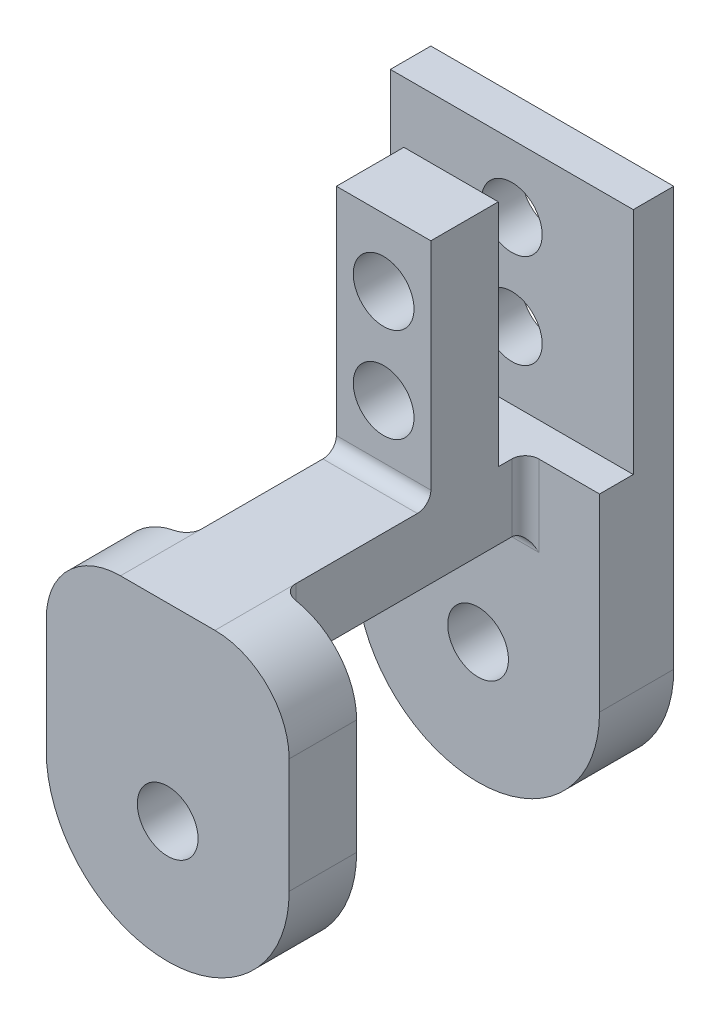
SolidWorks part; units mm, degrees
ref_plane "Plan de face" through (0, 0, 0) normal (0, 0, 1) x (1, 0, 0)
ref_plane "Plan de dessus" through (0, 0, 0) normal (0, 1, 0) x (1, 0, 0)
ref_plane "Plan de droite" through (0, 0, 0) normal (1, 0, 0) x (0, 0, -1)
sketch "Esquisse1" plane through (0, 0, 0) normal (0, 0, 1) x (1, 0, 0)
  line L0 (0, 17) -> (20, 17)
  line L1 (0, 0) -> (20, 0)
  line L2 (0, 0) -> (0, 25.6902)
  line L3 (0, 25.6902) -> (20, 25.6902)
  line L4 (20, 0) -> (20, 25.6902)
  circle A0 centre (10, 5) radius 2.1
  circle A1 centre (10, 12) radius 2.1
  point P15 (4.1099, 9.5645)
  dimension "D2" = 4.2
  dimension "D3" = 4.2
  dimension "D1" = 20
  dimension "D5" = 10
  dimension "D6" = 5
  dimension "D7" = 7
  dimension "D9" = 17
  dimension "D11" = 10
extrude "Boss.-Extru.1" add sketch "Esquisse1" along normal blind 5 contours L1 L4 L0 L2 A1 A0 region at (10, 8.5, 0)
sketch "Esquisse2" plane through (0, 0, 0) normal (0, -1, 0) x (1, 0, 0)
  line L0 (20, 5) -> (20, 0) construction
  line L1 (0, 0) -> (20, 0)
  line L2 (0, 0) -> (0, 5)
  line L3 (0, 5) -> (20, 5)
  line L4 (20, 0) -> (20, 5)
  line L5 (1, 5) -> (1, 0)
  line L6 (19, 5) -> (19, 0)
  line L7 (1, 3) -> (19, 3)
  line L9 (1, 0) -> (19, 0)
  line L10 (1, 0) -> (1, -5)
  line L11 (1, -5) -> (19, -5)
  line L12 (19, 0) -> (19, -5)
  line L13 (1, 0) -> (19, 0)
  line L14 (1, 0) -> (1, -2)
  line L15 (1, -2) -> (19, -2)
  line L16 (19, 0) -> (19, -2)
  point P11 (19, 2.5)
  dimension "D1" = 5
  dimension "D2" = 18
  dimension "D3" = 1
  dimension "D4" = 3
  dimension "D5" = 5
  dimension "D6" = 2
extrude "Boss.-Extru.3" add sketch "Esquisse2" along normal blind 23 contours L15 L10 L11 L12 region at (10, 0, -3.5)
sketch "Esquisse5" plane through (0, 0, 5) normal (0, 0, 1) x (1, 0, 0)
  line L0 (13.5, 17) -> (13.5, 0)
  line L1 (0, 17) -> (20, 17) construction
  line L2 (0, 0) -> (20, 0) construction
  line L3 (13.5, 0) -> (20, 0)
  line L4 (20, 0) -> (20, 17)
  line L5 (20, 0) -> (20, 17) construction
  line L6 (20, 17) -> (13.5, 17)
  line L8 (0, 0) -> (6.5, 0)
  line L9 (0, 0) -> (0, 17)
  line L10 (0, 17) -> (6.5, 17)
  line L11 (6.5, 0) -> (6.5, 17)
  dimension "D1" = 6.5
  dimension "D2" = 6.5
extrude "Enlèv. mat.-Extru.3" cut sketch "Esquisse5" against normal blind 18
sketch "Esquisse10" plane through (0, 0, 5) normal (0, 0, 1) x (1, 0, 0)
  line L1 (6.5, 0) -> (13.5, 0)
  line L2 (6.5, 0) -> (6.5, -3)
  line L3 (6.5, -3) -> (13.5, -3)
  line L4 (13.5, 0) -> (13.5, -3)
  dimension "D1" = 7
  dimension "D2" = 3
extrude "Boss.-Extru.6" add sketch "Esquisse10" against normal blind 10
sketch "Esquisse11" plane through (0, 0, 0) normal (0, 1, 0) x (1, 0, 0)
  line L0 (6.5, 2) -> (6.5, 0) construction
  line L1 (6.5, 0) -> (13.5, 0)
  line L2 (6.5, 0) -> (6.5, 5)
  line L3 (6.5, 5) -> (13.5, 5)
  line L4 (13.5, 0) -> (13.5, 5)
  line L5 (6.5, 0) -> (13.5, 0) construction
  line L6 (1, 5) -> (19, 5) construction
  line L8 (13.5, 4.5) -> (6.5, 4.5)
  line L9 (13.5, 4.5) -> (13.5, 0)
  line L10 (13.5, 0) -> (6.5, 0)
  line L11 (6.5, 4.5) -> (6.5, 0)
  line L12 (6.5, 4.5) -> (13.5, 4.5)
  line L13 (6.5, 4.5) -> (6.5, 7.5)
  line L14 (6.5, 7.5) -> (13.5, 7.5)
  line L15 (13.5, 4.5) -> (13.5, 7.5)
  line L16 (6.5, 4.5) -> (1, 4.5)
  line L17 (6.5, 4.5) -> (6.5, 7.5)
  line L18 (6.5, 7.5) -> (1, 7.5)
  line L19 (1, 4.5) -> (1, 7.5)
  line L20 (13.5, 4.5) -> (19, 4.5)
  line L21 (13.5, 4.5) -> (13.5, 7.5)
  line L22 (13.5, 7.5) -> (19, 7.5)
  line L23 (19, 4.5) -> (19, 7.5)
  line M12 (19, 2) -> (19, 5)
  line M13 (19, 5) -> (1, 5)
  line M14 (1, 5) -> (1, 2)
  dimension "D1" = 7
  dimension "D2" = 4.5
  dimension "D3" = 3
  dimension "D4" = 5.5
  dimension "D5" = 5.5
extrude "Boss.-Extru.7" add sketch "Esquisse11" along normal blind 17 contours L19 L13 L18 M13 | L15 L14 L13 M13 | L23 L22 L15 M13 | L16 L2 M13 M14 | L8 L4 L2 M13 | L4 L20 M12 M13 region at (3.75, 0, -4.75) region at (10, 0, -4.75) region at (16.25, 0, -4.75) region at (10, 0, -6.25) region at (3.75, 0, -6.25) region at (16.25, 0, -6.25)
sketch "Esquisse12" plane through (0, 0, 0) normal (0, -1, 0) x (1, 0, 0)
  line L5 (1, -5) -> (19, -5)
  line L6 (1, -5) -> (1, -7.5)
  line L7 (1, -7.5) -> (19, -7.5)
  line L8 (19, -5) -> (19, -7.5)
extrude "Boss.-Extru.8" add sketch "Esquisse12" along normal blind 23
fillet "Congé3" radius 9 2 edges at (19, -23, -4.75) (1, -23, -4.75)
sketch "Esquisse20" plane through (0, 0, 5) normal (0, 0, 1) x (1, 0, 0)
  circle A0 centre (10, 5) radius 2.25
  circle A1 centre (10, 12) radius 2.25
  dimension "D1" = 4.5
extrude "Enlèv. mat.-Extru.7" cut sketch "Esquisse20" against normal blind 18
sketch "Esquisse22" plane through (0, 0, -2) normal (0, 0, 1) x (1, 0, 0)
  line L1 (13.5, 0) -> (6.5, 0)
  line L2 (13.5, 0) -> (13.5, -5)
  line L3 (13.5, -5) -> (6.5, -5)
  line L4 (6.5, 0) -> (6.5, -5)
  dimension "D1" = 7
  dimension "D2" = 5
extrude "Boss.-Extru.9" add sketch "Esquisse22" along normal blind 23
sketch "Esquisse27" plane through (0, 0, 0) normal (0, 1, 0) x (1, 0, 0)
  line L1 (13.5, -21) -> (1, -21)
  line L2 (13.5, -21) -> (13.5, -16)
  line L3 (13.5, -16) -> (1, -16)
  line L4 (1, -21) -> (1, -16)
  line L5 (13.5, -16) -> (19, -16)
  line L6 (13.5, -16) -> (13.5, -21)
  line L7 (13.5, -21) -> (19, -21)
  line L8 (19, -16) -> (19, -21)
  line M5 (6.5, -5) -> (6.5, -21)
  line M6 (6.5, -21) -> (13.5, -21)
  line M7 (13.5, -21) -> (13.5, -5)
  dimension "D1" = 5
  dimension "D2" = 5
  dimension "D3" = 18
  dimension "D4" = 5.5
extrude "Boss.-Extru.10" add sketch "Esquisse27" against normal blind 23 contours L4 L1 L3 M5 | L8 L5 L7 M7 | L3 M7 M5 M6 region at (10, 0, 18.5) region at (16.25, 0, 18.5) region at (3.75, 0, 18.5)
fillet "Congé4" radius 9 2 edges at (1, -23, 18.5) (19, -23, 18.5)
sketch "Esquisse28" plane through (0, 0, 21) normal (0, 0, 1) x (1, 0, 0)
  line L0 (19, -14) -> (19, 0) construction
  circle A0 centre (10, -14) radius 2.25
  point P2 (0, 0)
  dimension "D1" = 4.5
  dimension "D2" = 9
  dimension "D3" = 9
extrude "Enlèv. mat.-Extru.8" cut sketch "Esquisse28" against normal blind 44
fillet "Congé5" radius 1 7 edges at (10, -5, 16) (10, -5, -2) (13.5, -2.5, 16) (13.5, -2.5, -2) (6.5, -2.5, -2) (6.5, -2.5, 16) (10, 0, 5)
fillet "Congé6" radius 5.5 2 edges at (1, 0, 18.5) (19, 0, 18.5)
